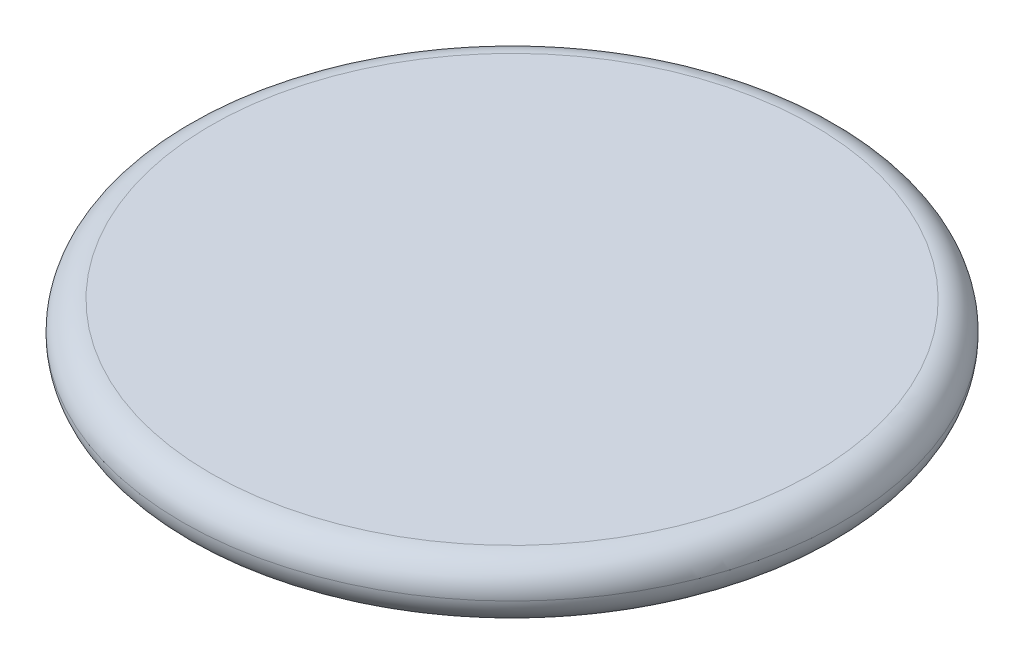
SolidWorks part; units mm, degrees
ref_plane "Front Plane" through (0, 0, 0) normal (0, 0, 1) x (1, 0, 0)
ref_plane "Top Plane" through (0, 0, 0) normal (0, 1, 0) x (1, 0, 0)
ref_plane "Right Plane" through (0, 0, 0) normal (1, 0, 0) x (0, 0, -1)
sketch "Sketch1" plane through (0, 0, 0) normal (0, 1, 0) x (1, 0, 0)
  circle A0 centre (0, 0) radius 2
  dimension "D1" = 4
extrude "Boss-Extrude1" add sketch "Sketch1" along normal blind 10
sketch "Sketch2" plane through (0, 10, 0) normal (0, 1, 0) x (1, 0, 0)
  circle A0 centre (0, 0) radius 17.5
  dimension "D1" = 35
extrude "Boss-Extrude2" add sketch "Sketch2" along normal blind 3
fillet "Fillet1" radius 1.5 2 edges at (0, 10, 17.5) (0, 13, 17.5)
